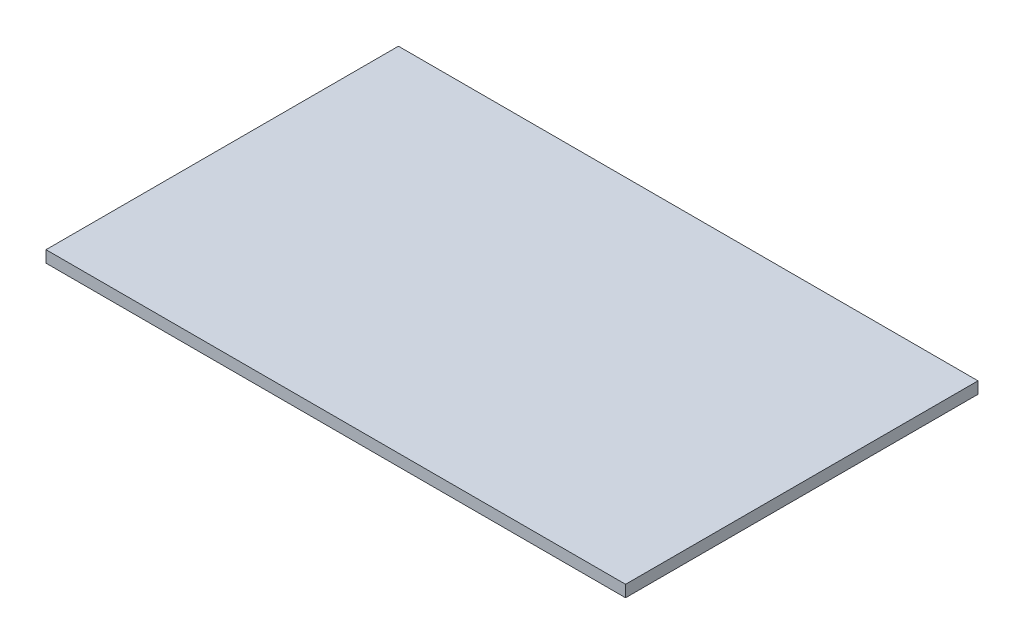
SolidWorks part; units mm, degrees
ref_plane "Front Plane" through (0, 0, 0) normal (0, 0, 1) x (1, 0, 0)
ref_plane "Top Plane" through (0, 0, 0) normal (0, 1, 0) x (1, 0, 0)
ref_plane "Right Plane" through (0, 0, 0) normal (1, 0, 0) x (0, 0, -1)
sketch "Sketch1" plane through (0, 0, 0) normal (0, 1, 0) x (1, 0, 0)
  line L1 (-62.8401, -38.2136) -> (62.8401, -38.2136)
  line L2 (-62.8401, -38.2136) -> (-62.8401, 38.2136)
  line L3 (-62.8401, 38.2136) -> (62.8401, 38.2136)
  line L4 (62.8401, -38.2136) -> (62.8401, 38.2136)
  line L5 (-62.8401, -38.2136) -> (62.8401, 38.2136) construction
  line L6 (-62.8401, 38.2136) -> (62.8401, -38.2136) construction
  point P0 (0, 0)
extrude "Boss-Extrude1" add sketch "Sketch1" along normal blind 2.54
